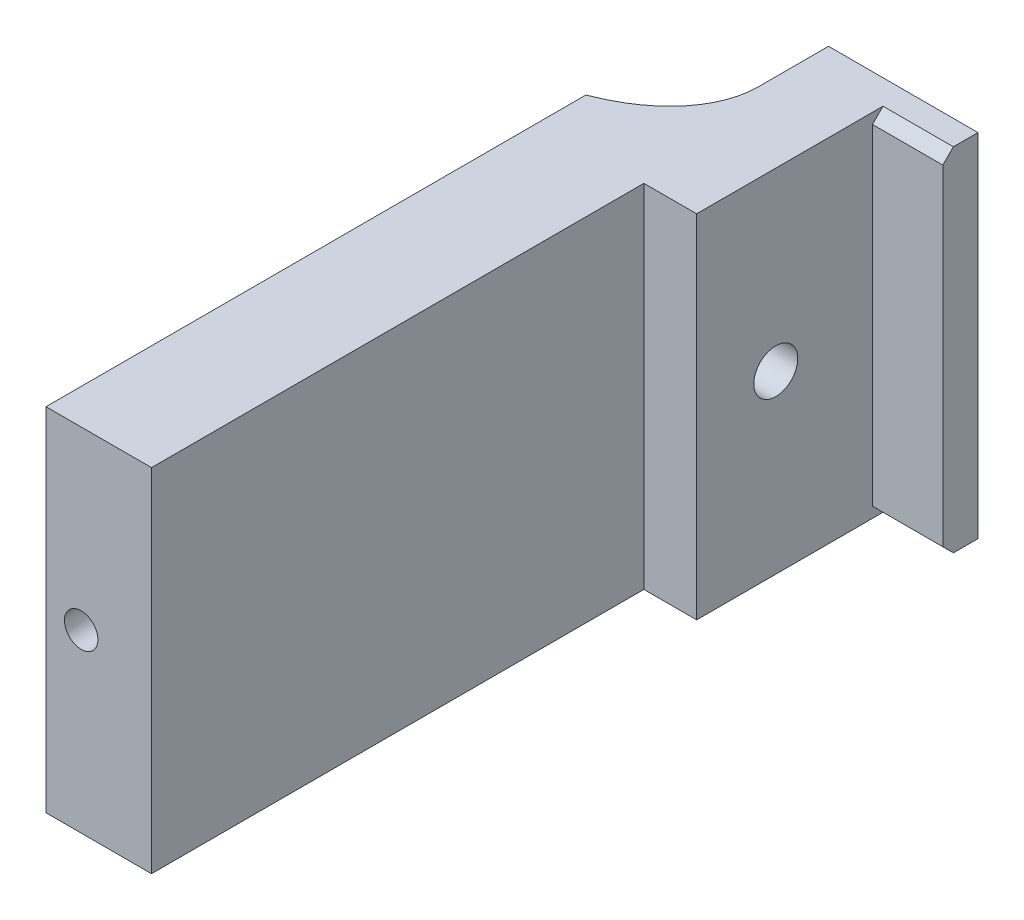
SolidWorks part; units mm, degrees
ref_plane "前视基准面" through (0, 0, 0) normal (0, 0, 1) x (1, 0, 0)
ref_plane "上视基准面" through (0, 0, 0) normal (0, 1, 0) x (1, 0, 0)
ref_plane "右视基准面" through (0, 0, 0) normal (1, 0, 0) x (0, 0, -1)
other "Configuration Table"
sketch "草图1" plane through (0, 0, 0) normal (0, 1, 0) x (1, 0, 0)
  line L0 (0, 0) -> (3, 0)
  line L1 (3, 0) -> (3, 10)
  line L2 (3, 10) -> (1, 10)
  line L3 (1, 10) -> (1, 2)
  line L4 (1, 2) -> (-2, 2)
  line L6 (-2, -26) -> (-6, -26)
  line L7 (-6, -26) -> (-6, -28)
  line L8 (-6, -28) -> (0, -28)
  line L9 (0, -28) -> (0, 0)
  line L12 (-2, 2) -> (-2, -26)
  dimension "D1" = 8
  dimension "D2" = 4
  dimension "D3" = 28
  dimension "D4" = 2
  dimension "D5" = 2
  dimension "D6" = 3
  dimension "D7" = 2
  dimension "D8" = 2
extrude "凸台-拉伸1" add sketch "草图1" along normal mid plane 20
sketch "草图2" plane through (1, 0, 0) normal (-1, 0, 0) x (0, 0, 1)
  line L0 (-4.5, 17.2009) -> (-4.5, -18.1104) construction
  line L2 (0, 0) -> (-13.8262, 0) construction
  line L3 (-2, 10) -> (-2, -10) construction
  circle A0 centre (-4.5, 0) radius 1.25
  dimension "D2" = 2.5
  dimension "D1" = 2.5
extrude "切除-拉伸1" cut sketch "草图2" against normal blind 15
sketch "草图4" plane through (0, 0, 28) normal (0, 0, 1) x (1, 0, 0)
  line L0 (-6, 0) -> (6.5775, 0) construction
  line L1 (-6, 10) -> (-6, -10) construction
  line L2 (-4, 12.0932) -> (-4, -13.8811) construction
  circle A0 centre (-4, 0) radius 0.95
  dimension "D2" = 1.9
  dimension "D1" = 2
extrude "切除-拉伸2" cut sketch "草图4" against normal through all
sketch "草图5" plane through (0, 0, 26) normal (0, 0, -1) x (-1, 0, 0)
  line L0 (2, 10) -> (6, 10)
  line L1 (6, 10) -> (6, -10) construction
  line L2 (2, 10) -> (6, 10) construction
  line L3 (6, 10) -> (2, 6)
  line L4 (2, 10) -> (2, -10) construction
  line L5 (2, 6) -> (2, 10)
  line L6 (0, 0) -> (10.5459, 0) construction
  line L7 (2, -6) -> (2, -10)
  line L8 (6, -10) -> (2, -6)
  line L9 (2, -10) -> (6, -10)
  dimension "D1" = 45
extrude "凸台-拉伸2" add sketch "草图5" along normal up to surface (28 mm away) up to face at (-0.5, 0, -2)
sketch "草图7" plane through (0, 0, -10) normal (0, 0, -1) x (-1, 0, 0)
  line L0 (-1, -10) -> (6, -10) construction
  line L1 (-1, 10) -> (-7, 10)
  line L2 (-1, 10) -> (-1, -10)
  line L3 (-1, -10) -> (-7, -10)
  line L4 (-7, 10) -> (-7, -10)
  line L5 (-1, 10) -> (-1, -10) construction
  dimension "D1" = 6
extrude "凸台-拉伸4" add sketch "草图7" along normal blind 2
chamfer "倒角1" distance 0.6 angle 45 2 edges at (5, -10, -10) (5, 10, -10)
sketch "草图8" plane through (0, 0, -2) normal (0, 0, -1) x (-1, 0, 0)
  line L0 (-1, 10) -> (1.5, 10)
  line L1 (-1, 10) -> (6, 10) construction
  line L2 (1.5, 10) -> (-1, 7.5)
  line L3 (-1, 10) -> (-1, -10) construction
  line L4 (-1, 7.5) -> (-1, 10)
  line L5 (-8.3664, 0) -> (9.2819, 0) construction
  line L6 (-1, -7.5) -> (-1, -10)
  line L7 (1.5, -10) -> (-1, -7.5)
  line L8 (-1, -10) -> (1.5, -10)
  dimension "D1" = 2.5
  dimension "D2" = 45
extrude "凸台-拉伸5" add sketch "草图8" along normal up to surface (10 mm away) up to face at (4, 0, -12)
fillet "圆角2" radius 6 2 edges at (-0.25, -8.75, -2) (-0.25, 8.75, -2)
